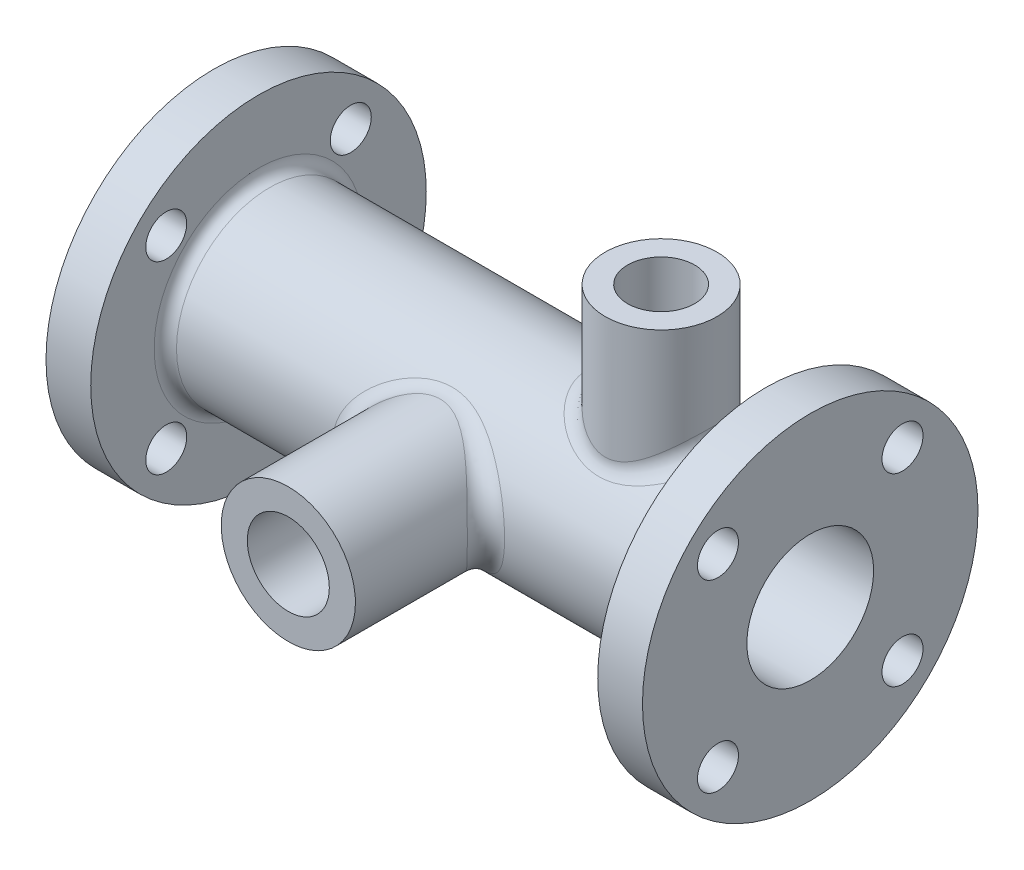
SolidWorks part; units mm, degrees
ref_plane "前视基准面" through (0, 0, 0) normal (0, 0, 1) x (1, 0, 0)
ref_plane "上视基准面" through (0, 0, 0) normal (0, 1, 0) x (1, 0, 0)
ref_plane "右视基准面" through (0, 0, 0) normal (1, 0, 0) x (0, 0, -1)
ref_plane "基准面1" through (-80, 0, 0) normal (1, 0, 0) x (0, 0, -1)
sketch "草图1" plane through (-80, 0, 0) normal (1, 0, 0) x (0, 0, -1)
  circle A0 centre (0, 0) radius 25
extrude "凸台-拉伸1" add sketch "草图1" along normal blind 160
sketch "草图2" plane through (-80, 0, 0) normal (1, 0, 0) x (0, 0, -1)
  circle A0 centre (0, 0) radius 45
extrude "凸台-拉伸2" add sketch "草图2" along normal blind 12
ref_plane "基准面2" through (80, 0, 0) normal (1, 0, 0) x (0, 0, -1)
sketch "草图3" plane through (80, 0, 0) normal (1, 0, 0) x (0, 0, -1)
  circle A0 centre (0, 0) radius 45
extrude "凸台-拉伸3" add sketch "草图3" against normal blind 12
sketch "草图4" plane through (0, 0, 0) normal (0, 0, 1) x (1, 0, 0)
  circle A0 centre (0, 0) radius 18
extrude "凸台-拉伸4" add sketch "草图4" along normal blind 60
sketch "草图5" plane through (0, 0, 0) normal (0, 1, 0) x (1, 0, 0)
  circle A0 centre (40, 0) radius 15
extrude "凸台-拉伸5" add sketch "草图5" along normal blind 55
sketch "草图6" plane through (-80, 0, 0) normal (1, 0, 0) x (0, 0, -1)
  circle A0 centre (0, 0) radius 17
extrude "切除-拉伸1" cut sketch "草图6" along normal through all
ref_plane "基准面3" through (0, 0, 60) normal (0, 0, 1) x (1, 0, 0)
sketch "草图7" plane through (0, 0, 60) normal (0, 0, 1) x (1, 0, 0)
  circle A0 centre (0, 0) radius 11
extrude "切除-拉伸2" cut sketch "草图7" against normal blind 60
ref_plane "基准面4" through (0, 55, 0) normal (0, 1, 0) x (1, 0, 0)
sketch "草图8" plane through (0, 55, 0) normal (0, 1, 0) x (1, 0, 0)
  circle A0 centre (40, 0) radius 9
extrude "切除-拉伸3" cut sketch "草图8" against normal blind 55
sketch "草图9" plane through (-80, 0, 0) normal (1, 0, 0) x (0, 0, -1)
  circle A0 centre (-24.749, 24.749) radius 5.5
  circle A1 centre (-24.749, -24.749) radius 5.5
  circle A2 centre (24.749, 24.749) radius 5.5
  circle A3 centre (24.749, -24.749) radius 5.5
extrude "切除-拉伸4" cut sketch "草图9" along normal through all
fillet "圆角1" radius 5 2 edges at (39.9676, 20, 15) (-17.7147, -3.1921, 24.7954)
fillet "圆角2" radius 3 2 edges at (68, 0, -25) (-68, 0, -25)
